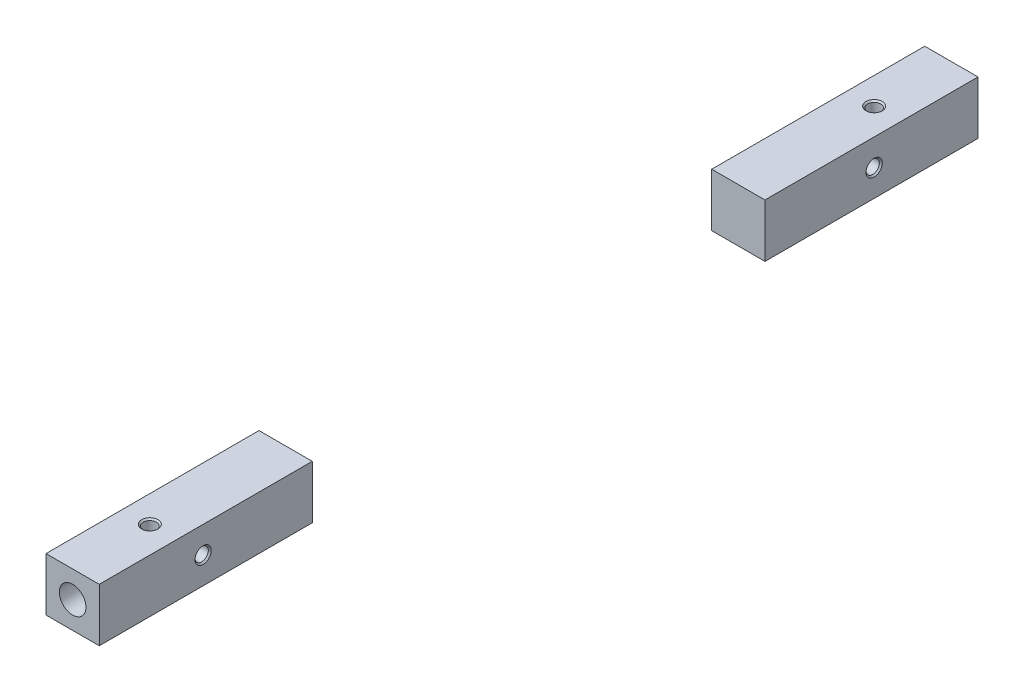
SolidWorks part; units mm, degrees
ref_plane "Plan de face" through (0, 0, 0) normal (0, 0, 1) x (1, 0, 0)
ref_plane "Plan de dessus" through (0, 0, 0) normal (0, 1, 0) x (1, 0, 0)
ref_plane "Plan de droite" through (0, 0, 0) normal (1, 0, 0) x (0, 0, -1)
sketch "Esquisse1" plane through (0, 0, 0) normal (0, 0, 1) x (1, 0, 0)
  line L0 (-5, 5) -> (5, -5) construction
  line L1 (-5, 5) -> (5, 5)
  line L2 (-5, 5) -> (-5, -5)
  line L3 (-5, -5) -> (5, -5)
  line L4 (5, 5) -> (5, -5)
  dimension "D1" = 10
extrude "Boss.-Extru.1" add sketch "Esquisse1" along normal mid plane 165
hole_wizard "Trou taraudé M3x0.51" positions "Esquisse3" profile "Esquisse2" tap size "M3x0.5" standard "Ansi Metric" end condition through all
sketch "Esquisse3" plane through (5, 0, 0) normal (1, 0, 0) x (0, 0, -1)
  point P0 (63, 0)
  point P3 (-63, 0)
sketch "Esquisse2" plane through (5, 0, -63) normal (0, 1, 0) x (0, 0, -1)
  line L0 (0, 0) -> (0, 10)
  line L1 (0, 10) -> (1.25, 10)
  line L2 (1.25, 10) -> (1.25, 0.275)
  line L3 (1.25, 0.275) -> (1.525, 0)
  line L5 (1.525, 0) -> (0, 0)
  line L6 (-1.25, 0.275) -> (-1.525, 0) construction
  line L11 (0, -6.35) -> (0, 107.95) construction
  dimension "Diamètre du trou pour taraudage jusqu'au prochain" = 2.5
  dimension "Profondeur du trou pour taraudage jusqu'au prochain" = 10
  dimension "Diamètre du fraisage entrant" = 3.05
  dimension "Angle du fraisage entrant" = 90
cosmetic thread "Filetage de perçage1" parameters "D2"=3
cosmetic thread "Filetage de perçage2" parameters "D2"=3
hole_wizard "Trou taraudé M3x0.52" positions "Esquisse5" profile "Esquisse4" tap size "M3x0.5" standard "Ansi Metric" end condition through all
sketch "Esquisse5" plane through (0, 5, 0) normal (0, 1, 0) x (1, 0, 0)
  line L0 (0, 0) -> (-36.1539, 0) construction
  line L2 (5, 82.5) -> (-5, 82.5) construction
  point P0 (0, 68)
  point P2 (0, -68)
  dimension "D1" = 68
  dimension "D2" = 14.5
sketch "Esquisse4" plane through (0, 5, -68) normal (1, 0, 0) x (0, 0, 1)
  line L0 (0, 0) -> (0, 10)
  line L1 (0, 10) -> (1.25, 10)
  line L2 (1.25, 10) -> (1.25, 0.275)
  line L3 (1.25, 0.275) -> (1.525, 0)
  line L5 (1.525, 0) -> (0, 0)
  line L6 (-1.25, 0.275) -> (-1.525, 0) construction
  line L11 (0, -6.35) -> (0, 107.95) construction
  dimension "Diamètre du trou pour taraudage jusqu'au prochain" = 2.5
  dimension "Profondeur du trou pour taraudage jusqu'au prochain" = 10
  dimension "Diamètre du fraisage entrant" = 3.05
  dimension "Angle du fraisage entrant" = 90
cosmetic thread "Filetage de perçage3" parameters "D2"=3
cosmetic thread "Filetage de perçage4" parameters "D2"=3
sketch "Esquisse6" plane through (0, 0, 82.5) normal (0, 0, 1) x (1, 0, 0)
  circle A0 centre (0, 0) radius 2.5
  dimension "D1" = 5
extrude "Enlèv. mat.-Extru.1" cut sketch "Esquisse6" against normal blind 6
sketch "Esquisse7" plane through (0, 0, -82.5) normal (0, 0, -1) x (-1, 0, 0)
  circle A0 centre (0, 0) radius 2.5
  dimension "D1" = 5
extrude "Enlèv. mat.-Extru.2" cut sketch "Esquisse7" against normal blind 6
sketch "Esquisse8" plane through (0, 5, 0) normal (0, 1, 0) x (1, 0, 0)
  line L0 (-5, -82.5) -> (-5, 82.5) construction
  line L1 (-5, -42.5) -> (5, -42.5)
  line L2 (-5, -42.5) -> (-5, 42.5)
  line L3 (-5, 42.5) -> (5, 42.5)
  line L4 (5, -42.5) -> (5, 42.5)
  line L5 (5, -82.5) -> (5, 82.5) construction
  line L6 (5, -82.5) -> (-5, -82.5) construction
  line L7 (5, 82.5) -> (-5, 82.5) construction
  point P10 (0, -82.5)
  dimension "D1" = 40
  dimension "D2" = 40
extrude "Enlèv. mat.-Extru.3" cut sketch "Esquisse8" against normal through all
